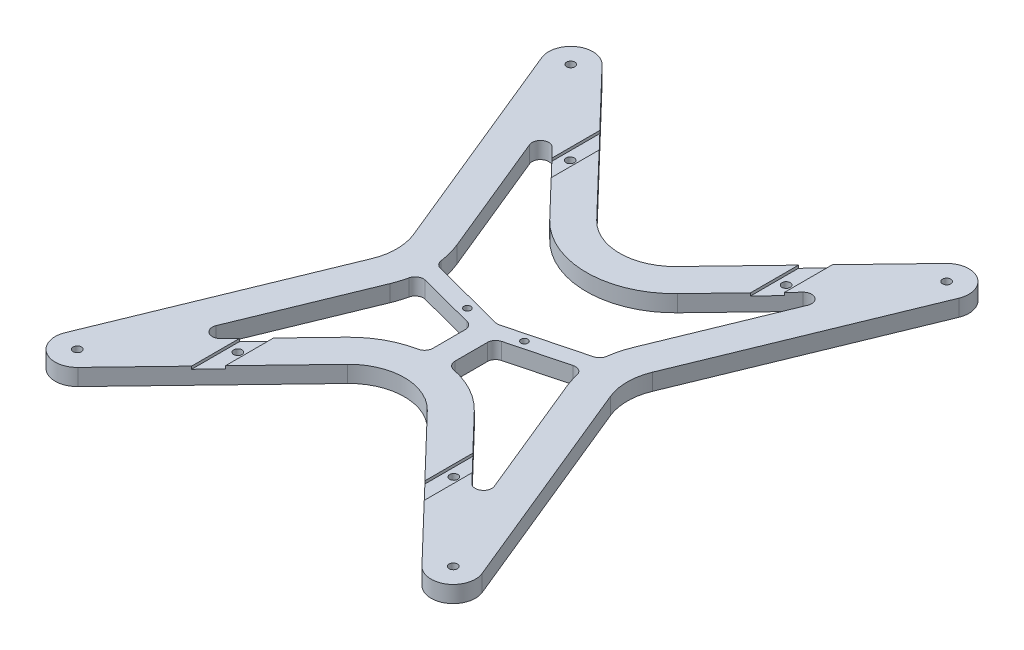
SolidWorks part; units mm, degrees
material "1060 Alloy"
ref_plane "Front Plane" through (0, 0, 0) normal (0, 0, 1) x (1, 0, 0)
ref_plane "Top Plane" through (0, 0, 0) normal (0, 1, 0) x (1, 0, 0)
ref_plane "Right Plane" through (0, 0, 0) normal (1, 0, 0) x (0, 0, -1)
sketch "Sketch1" plane through (0, 0, 0) normal (0, 1, 0) x (1, 0, 0)
  line L0 (-62.1139, 94.6385) -> (0, 30)
  line L1 (0, 30) -> (62.1139, 94.6385)
  line L2 (75.2843, 86.0607) -> (40, 0)
  line L3 (40, 0) -> (75.2843, -86.0607)
  line L4 (62.1139, -94.6385) -> (0, -30)
  line L5 (0, -30) -> (-62.1139, -94.6385)
  line L6 (-75.2843, -86.0607) -> (-40, 0)
  line L7 (-40, 0) -> (-75.2843, 86.0607)
  line L8 (-78.4889, 78.4889) -> (78.4889, -78.4889) construction
  line L9 (-42, 70) -> (-36, 70) construction
  line L10 (-42, 70) -> (-42, 50) construction
  line L11 (-42, 50) -> (-36, 50) construction
  line L12 (-36, 70) -> (-36, 50) construction
  line L13 (-42, 70) -> (-36, 50) construction
  line L14 (-42, 50) -> (-36, 70) construction
  line L15 (36, 70) -> (42, 70) construction
  line L16 (36, 70) -> (36, 50) construction
  line L17 (36, 50) -> (42, 50) construction
  line L18 (42, 70) -> (42, 50) construction
  line L19 (36, 70) -> (42, 50) construction
  line L20 (36, 50) -> (42, 70) construction
  line L21 (36, -50) -> (42, -50) construction
  line L22 (36, -50) -> (36, -70) construction
  line L23 (36, -70) -> (42, -70) construction
  line L24 (42, -50) -> (42, -70) construction
  line L25 (36, -50) -> (42, -70) construction
  line L26 (36, -70) -> (42, -50) construction
  line L27 (-42, -50) -> (-36, -50) construction
  line L28 (-42, -50) -> (-42, -70) construction
  line L29 (-42, -70) -> (-36, -70) construction
  line L30 (-36, -50) -> (-36, -70) construction
  line L31 (-42, -50) -> (-36, -70) construction
  line L32 (-42, -70) -> (-36, -50) construction
  line L33 (111, 45.9777) -> (45.9777, 111) construction
  line L34 (45.9777, 111) -> (-45.9777, 111) construction
  line L35 (-45.9777, 111) -> (-111, 45.9777) construction
  line L36 (-111, 45.9777) -> (-111, -45.9777) construction
  line L37 (-111, -45.9777) -> (-45.9777, -111) construction
  line L38 (-45.9777, -111) -> (45.9777, -111) construction
  line L39 (45.9777, -111) -> (111, -45.9777) construction
  line L40 (111, -45.9777) -> (111, 45.9777) construction
  line L41 (78.4889, 78.4889) -> (-78.4889, -78.4889) construction
  circle A0 centre (-67.8823, 89.0955) radius 1.5
  circle A1 centre (67.8823, 89.0955) radius 1.5
  circle A2 centre (-67.8823, -89.0955) radius 1.5
  circle A3 centre (67.8823, -89.0955) radius 1.5
  arc A4 (-62.1139, 94.6385) -> (-75.2843, 86.0607) centre (-67.8823, 89.0955) ccw
  arc A5 (62.1139, 94.6385) -> (75.2843, 86.0607) centre (67.8823, 89.0955) cw
  arc A6 (-75.2843, -86.0607) -> (-62.1139, -94.6385) centre (-67.8823, -89.0955) ccw
  arc A7 (75.2843, -86.0607) -> (62.1139, -94.6385) centre (67.8823, -89.0955) cw
  circle A8 centre (0, 0) radius 111 construction
  circle A9 centre (-39, 60) radius 1.5
  circle A10 centre (39, 60) radius 1.5
  circle A11 centre (39, -60) radius 1.5
  circle A12 centre (-39, -60) radius 1.5
  ellipse E0 centre (0, 0) end of major axis (-40, 0) minor radius 30 construction
  dimension "D5" = 3
  dimension "D6" = 30
  dimension "D7" = 8
  dimension "D12" = 3
  dimension "D3" = 15
  dimension "D4" = 15
  dimension "D8" = 120
  dimension "D9" = 78
  dimension "D10" = 0
  dimension "D11" = 60
  dimension "D13" = 40
  dimension "D14" = 39
  dimension "D15" = 20
  dimension "D16" = 6
  dimension "D17" = 111
  dimension "D18" = 15
extrude "Boss-Extrude1" add sketch "Sketch1" along normal blind 6
fillet "Fillet1" radius 20 4 edges at (0, 3, -30) (-40, 3, 0) (0, 3, 30) (40, 3, 0)
sketch "Sketch2" plane through (0, 6, 0) normal (0, 1, 0) x (1, 0, 0)
  line L44 (-56.2138, 71.1798) -> (-32.0076, 12.1391)
  line L45 (-32.0076, -12.1391) -> (-56.2138, -71.1798)
  line L46 (-56.2138, -71.1798) -> (-23.0735, -36.6925)
  line L47 (23.0735, -36.6925) -> (56.2138, -71.1798)
  line L48 (56.2138, -71.1798) -> (32.0076, -12.1391)
  line L49 (32.0076, 12.1391) -> (56.2138, 71.1798)
  line L50 (56.2138, 71.1798) -> (23.0735, 36.6925)
  line L51 (-23.0735, 36.6925) -> (-56.2138, 71.1798)
  line L52 (-56.2138, 71.1798) -> (-32.0076, 12.1391)
  line L53 (-32.0076, -12.1391) -> (-56.2138, -71.1798)
  line L54 (-56.2138, -71.1798) -> (-23.0735, -36.6925)
  line L55 (23.0735, -36.6925) -> (56.2138, -71.1798)
  line L56 (56.2138, -71.1798) -> (32.0076, -12.1391)
  line L57 (32.0076, 12.1391) -> (56.2138, 71.1798)
  line L58 (56.2138, 71.1798) -> (23.0735, 36.6925)
  line L59 (-23.0735, 36.6925) -> (-56.2138, 71.1798)
  arc A40 (-32.0076, -12.1391) -> (-32.0076, 12.1391) centre (-61.6157, 0) ccw
  arc A41 (23.0735, -36.6925) -> (-23.0735, -36.6925) centre (0, -58.8648) ccw
  arc A42 (32.0076, 12.1391) -> (32.0076, -12.1391) centre (61.6157, 0) ccw
  arc A43 (-23.0735, 36.6925) -> (23.0735, 36.6925) centre (0, 58.8648) ccw
  arc A44 (-32.0076, -12.1391) -> (-32.0076, 12.1391) centre (-61.6157, 0) ccw
  arc A45 (23.0735, -36.6925) -> (-23.0735, -36.6925) centre (0, -58.8648) ccw
  arc A46 (32.0076, 12.1391) -> (32.0076, -12.1391) centre (61.6157, 0) ccw
  arc A47 (-23.0735, 36.6925) -> (23.0735, 36.6925) centre (0, 58.8648) ccw
  dimension "D1" = 12
extrude "Cut-Extrude1" cut sketch "Sketch2" against normal up to next
sketch "Sketch5" plane through (0, 6, 0) normal (0, 1, 0) x (1, 0, 0)
  line L0 (-31.8574, 2.9026) -> (0, -5.4202)
  line L1 (-12.94, -8.43) -> (12.94, -8.43) construction
  line L2 (-12.94, -8.43) -> (-12.94, 8.43) construction
  line L3 (-12.94, 8.43) -> (12.94, 8.43) construction
  line L4 (12.94, -8.43) -> (12.94, 8.43) construction
  line L5 (-12.94, -8.43) -> (12.94, 8.43) construction
  line L6 (-12.94, 8.43) -> (12.94, -8.43) construction
  line L8 (0, -5.4202) -> (31.8574, 2.9026)
  line L10 (31.8574, 2.9026) -> (33.374, -2.9026)
  line L11 (33.374, -2.9026) -> (4, -10.5766)
  line L12 (4, -10.5766) -> (4, -27.1158)
  line L13 (-4, -27.1158) -> (-4, -10.5766)
  line L14 (-4, -10.5766) -> (-33.374, -2.9026)
  line L15 (-33.374, -2.9026) -> (-31.8574, 2.9026)
  line L17 (32.6157, 0) -> (-32.6157, 0) construction
  circle A0 centre (-10.3, -5.83) radius 1.25
  circle A1 centre (10.3, -5.83) radius 1.25
  arc A2 (23.0735, -36.6925) -> (-23.0735, -36.6925) centre (0, -58.8648) ccw construction
  arc A3 (4, -27.1158) -> (-4, -27.1158) centre (0, -58.8648) ccw
  arc A4 (-32.0076, -12.1391) -> (-32.0076, 12.1391) centre (-61.6157, 0) ccw construction
  arc A5 (32.0076, 12.1391) -> (32.0076, -12.1391) centre (61.6157, 0) ccw construction
  circle A6 centre (32.6157, 0) radius 3 construction
  circle A7 centre (-32.6157, 0) radius 3 construction
  point P0 (0, 0)
  dimension "D3" = 2.5
  dimension "D10" = 6
  dimension "D1" = 16.86
  dimension "D2" = 25.88
  dimension "D4" = 20.6
  dimension "D5" = 2.64
  dimension "D6" = 2.6
  dimension "D7" = 6
  dimension "D8" = 3
  dimension "D9" = 8
extrude "Boss-Extrude2" add sketch "Sketch5" against normal up to surface (6 mm away) up to face at (0, 0, 0)
fillet "Fillet2" radius 3 13 edges at (56.2138, 3, 71.1798) (-56.2138, 3, 71.1798) (56.2138, 3, -71.1798) (-56.2138, 3, -71.1798) (0, 3, 5.4202) (4, 3, 10.5766) (4, 3, 27.1158) (-4, 3, 27.1158) (-4, 3, 10.5766) (29.7013, 3, -2.3393) (-29.7013, 3, -2.3393) (29.8451, 3, 3.8245) (-29.8451, 3, 3.8245)
sketch "Sketch6" plane through (0, 6, 0) normal (0, 1, 0) x (1, 0, 0)
  line L0 (-14.421, 45.0071) -> (-62.1139, 94.6385) construction
  line L1 (-42, -48) -> (-36, -48)
  line L2 (-42, -48) -> (-42, -73.7071)
  line L3 (-42, -73.7071) -> (-36, -73.7071)
  line L4 (-36, -48) -> (-36, -73.7071)
  line L5 (36, -48) -> (42, -48)
  line L6 (36, -48) -> (36, -73.7071)
  line L7 (36, -73.7071) -> (42, -73.7071)
  line L8 (42, -48) -> (42, -73.7071)
  line L9 (36, 48) -> (42, 48)
  line L10 (36, 48) -> (36, 73.7071)
  line L11 (36, 73.7071) -> (42, 73.7071)
  line L12 (42, 48) -> (42, 73.7071)
  line L13 (-42, 48) -> (-36, 48)
  line L14 (-42, 48) -> (-42, 73.7071)
  line L15 (-42, 73.7071) -> (-36, 73.7071)
  line L16 (-36, 48) -> (-36, 73.7071)
  line L17 (62.1139, 94.6385) -> (14.421, 45.0071) construction
  line L18 (14.421, -45.0071) -> (62.1139, -94.6385) construction
  line L19 (-62.1139, -94.6385) -> (-14.421, -45.0071) construction
  circle A0 centre (-39, -60) radius 1.5 construction
  circle A1 centre (39, -60) radius 1.5 construction
  circle A2 centre (-39, 60) radius 1.5 construction
  dimension "D2" = 3
  dimension "D3" = 3
  dimension "D5" = 12
  dimension "D1" = 6
  dimension "D4" = 12
extrude "Cut-Extrude2" cut sketch "Sketch6" against normal blind 1
equation "\"D14@Sketch1\"=\"D9@Sketch1\"/2"
